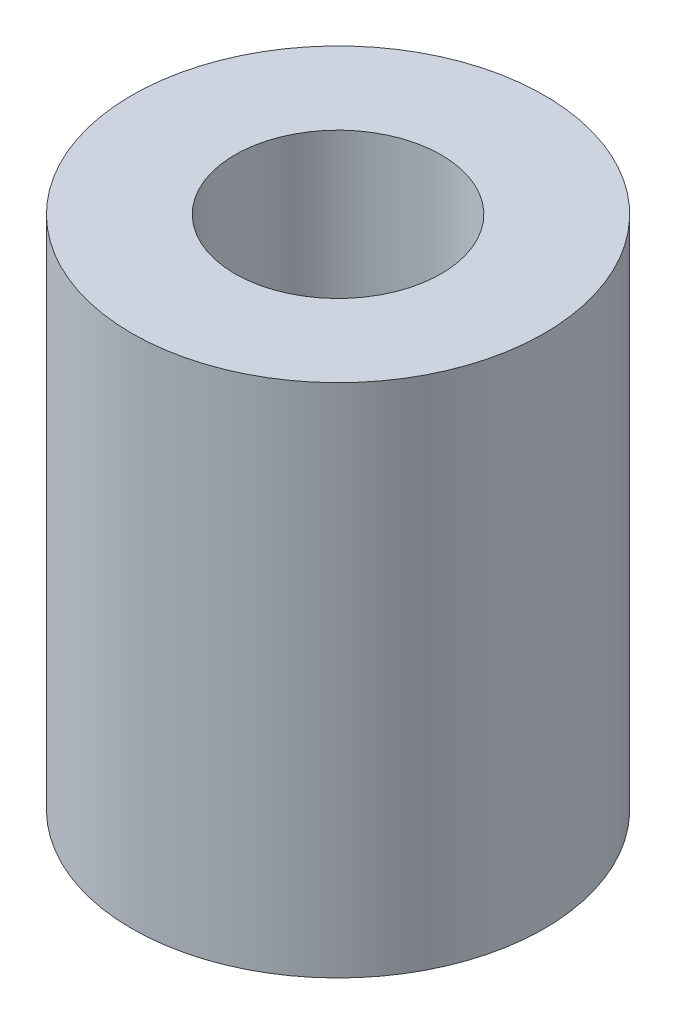
SolidWorks part; units mm, degrees
ref_plane "Front Plane" through (0, 0, 0) normal (0, 0, 1) x (1, 0, 0)
ref_plane "Top Plane" through (0, 0, 0) normal (0, 1, 0) x (1, 0, 0)
ref_plane "Right Plane" through (0, 0, 0) normal (1, 0, 0) x (0, 0, -1)
sketch "Sketch2" plane through (0, 0, 0) normal (0, 1, 0) x (1, 0, 0)
  circle A0 centre (0, -0.0185) radius 3
  circle A1 centre (0, -0.0185) radius 1.5
  dimension "D1" = 6
  dimension "D2" = 3
extrude "Boss-Extrude1" add sketch "Sketch2" along normal blind 7.5
